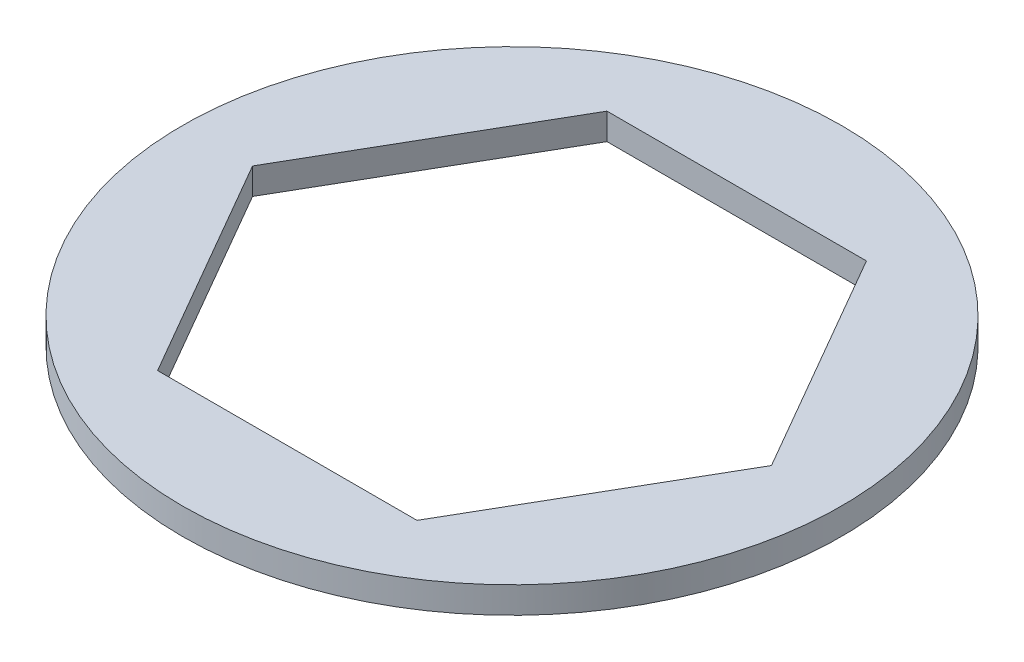
SolidWorks part; units mm, degrees
material "PET"
ref_plane "Front Plane" through (0, 0, 0) normal (0, 0, 1) x (1, 0, 0)
ref_plane "Top Plane" through (0, 0, 0) normal (0, 1, 0) x (1, 0, 0)
ref_plane "Right Plane" through (0, 0, 0) normal (1, 0, 0) x (0, 0, -1)
sketch "Sketch1" plane through (0, 0, 0) normal (0, 1, 0) x (1, 0, 0)
  line L7 (7.479, 0) -> (3.7395, 6.477)
  line L8 (3.7395, 6.477) -> (-3.7395, 6.477)
  line L9 (-3.7395, 6.477) -> (-7.479, 0)
  line L10 (-7.479, 0) -> (-3.7395, -6.477)
  line L11 (-3.7395, -6.477) -> (3.7395, -6.477)
  line L12 (3.7395, -6.477) -> (7.479, 0)
  circle A0 centre (0, 0) radius 6.477 construction
  circle A7 centre (0, 0) radius 9.5
  dimension "D1" = 12.954
  dimension "D2" = 19
extrude "Boss-Extrude1" add sketch "Sketch1" against normal blind 0.762
